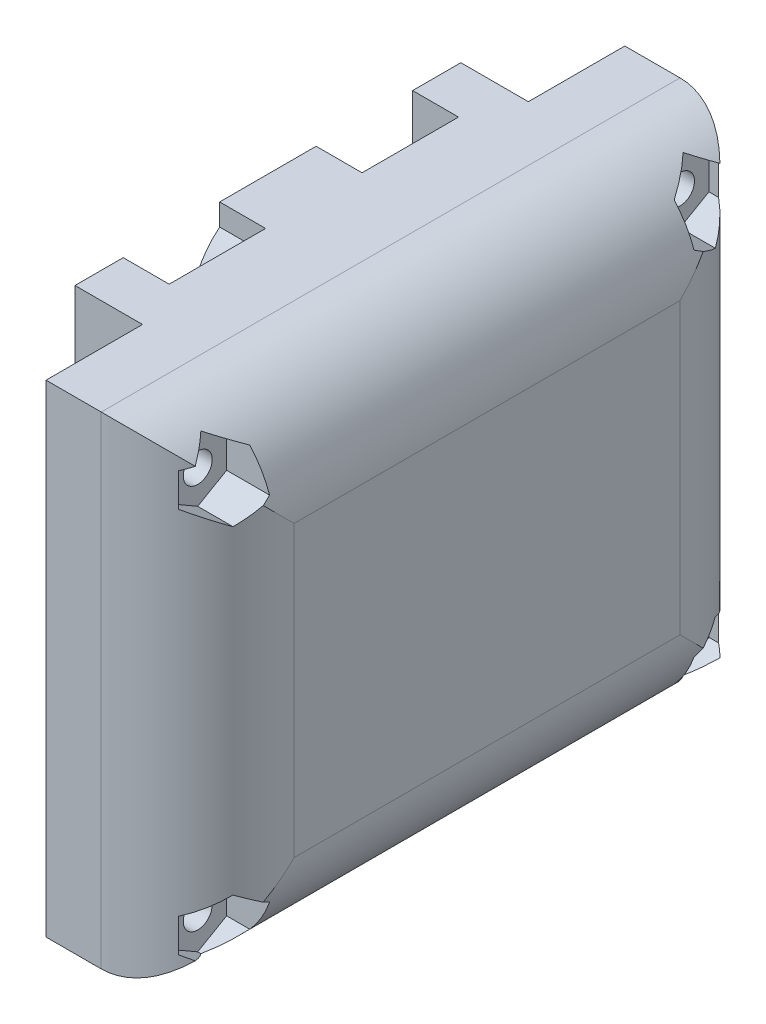
SolidWorks part; units mm, degrees
ref_plane "Alzado" through (0, 0, 0) normal (0, 0, 1) x (1, 0, 0)
ref_plane "Planta" through (0, 0, 0) normal (0, 1, 0) x (1, 0, 0)
ref_plane "Vista lateral" through (0, 0, 0) normal (1, 0, 0) x (0, 0, -1)
sketch "Croquis1" plane through (0, 0, 0) normal (1, 0, 0) x (0, 0, -1)
  line L0 (0, 0) -> (0, 16.1453) construction
  line L1 (-30, -25) -> (30, -25)
  line L2 (-30, -25) -> (-30, 25)
  line L3 (-30, 25) -> (30, 25)
  line L4 (30, -25) -> (30, 25)
  line L5 (-30, -25) -> (30, 25) construction
  line L6 (-30, 25) -> (30, -25) construction
  line L7 (0, 0) -> (-19.1227, 0) construction
  circle A0 centre (-25, 20) radius 1.5
  circle A1 centre (25, 20) radius 1.5
  circle A2 centre (25, -20) radius 1.5
  circle A3 centre (-25, -20) radius 1.5
  point P0 (0, 0)
  dimension "D3" = 3
  dimension "D1" = 60
  dimension "D2" = 50
  dimension "D4" = 5
  dimension "D5" = 5
extrude "Saliente-Extruir1" add sketch "Croquis1" along normal blind 17.96
sketch "Croquis3" plane through (0, 0, 0) normal (-1, 0, 0) x (0, 0, 1)
  line L0 (30, -25) -> (-30, -25) construction
  line L1 (-30, 25) -> (-15, 25)
  line L2 (-30, 25) -> (-30, -25)
  line L3 (-30, -25) -> (-15, -25)
  line L4 (-15, 25) -> (-15, -25)
  line L5 (0, 0) -> (0, -25) construction
  line L6 (30, -25) -> (15, -25)
  line L7 (15, 25) -> (15, -25)
  line L8 (30, 25) -> (15, 25)
  line L9 (30, 25) -> (30, -25)
  circle A0 centre (25, -20) radius 1.5 construction
  circle A1 centre (25, 20) radius 1.5 construction
  circle A2 centre (-25, -20) radius 1.5 construction
  circle A3 centre (-25, 20) radius 1.5 construction
  circle A4 centre (25, -20) radius 1.5
  circle A5 centre (25, 20) radius 1.5
  circle A6 centre (-25, -20) radius 1.5
  circle A7 centre (-25, 20) radius 1.5
  dimension "D1" = 30
extrude "Saliente-Extruir2" add sketch "Croquis3" along normal blind 4.7625
sketch "Croquis4" plane through (0, 0, 0) normal (-1, 0, 0) x (0, 0, 1)
  line L0 (0, 16.5) -> (0, -16.5) construction
  line L1 (-15, 25) -> (15, 25) construction
  line L3 (-5, 22.745) -> (-5, 25)
  line L4 (-5, 25) -> (5, 25)
  line L5 (5, 22.745) -> (5, 25)
  line L6 (-4.0562, 9.6045) -> (4.0562, 23.3955) construction
  line L7 (-4.0562, 23.3955) -> (4.0562, 9.6045) construction
  line L9 (-5, -22.745) -> (-5, -25)
  line L10 (-5, -25) -> (5, -25)
  line L11 (5, -22.745) -> (5, -25)
  line L12 (-4.0562, -9.6045) -> (5, -25) construction
  line L13 (-5, -25) -> (4.0562, -9.6045) construction
  line L14 (15, -25) -> (-15, -25) construction
  arc A0 (-5, 22.745) -> (5, 22.745) centre (0, 16.5) ccw
  arc A1 (5, -22.745) -> (-5, -22.745) centre (0, -16.5) ccw
  point P6 (0, 0)
  dimension "D1" = 16
  dimension "D2" = 16
  dimension "D3" = 33
  dimension "D4" = 10
  dimension "D5" = 10
extrude "Saliente-Extruir3" add sketch "Croquis4" along normal blind 4.7625
fillet "Redondeo2" radius 10 4 edges at (17.96, 0, -30) (17.96, 25, 0) (17.96, -25, 0) (17.96, 0, 30)
sketch "Croquis5" plane through (17.96, 0, 0) normal (1, 0, 0) x (0, 0, -1)
  line L1 (-25, 23.4641) -> (-28, 21.7321)
  line L2 (-28, 21.7321) -> (-28, 18.2679)
  line L3 (-28, 18.2679) -> (-25, 16.5359)
  line L4 (-25, 16.5359) -> (-22, 18.2679)
  line L5 (-22, 18.2679) -> (-22, 21.7321)
  line L6 (-22, 21.7321) -> (-25, 23.4641)
  line L7 (25, 23.4641) -> (22, 21.7321)
  line L8 (22, 21.7321) -> (22, 18.2679)
  line L9 (22, 18.2679) -> (25, 16.5359)
  line L10 (25, 16.5359) -> (28, 18.2679)
  line L11 (28, 18.2679) -> (28, 21.7321)
  line L12 (28, 21.7321) -> (25, 23.4641)
  line L13 (25, -16.5359) -> (22, -18.2679)
  line L14 (22, -18.2679) -> (22, -21.7321)
  line L15 (22, -21.7321) -> (25, -23.4641)
  line L16 (25, -23.4641) -> (28, -21.7321)
  line L17 (28, -21.7321) -> (28, -18.2679)
  line L18 (28, -18.2679) -> (25, -16.5359)
  line L19 (-25, -16.5359) -> (-28, -18.2679)
  line L20 (-28, -18.2679) -> (-28, -21.7321)
  line L21 (-28, -21.7321) -> (-25, -23.4641)
  line L22 (-25, -23.4641) -> (-22, -21.7321)
  line L23 (-22, -21.7321) -> (-22, -18.2679)
  line L24 (-22, -18.2679) -> (-25, -16.5359)
  circle A0 centre (-25, 20) radius 3 construction
  circle A1 centre (25, 20) radius 3 construction
  circle A2 centre (25, -20) radius 3 construction
  circle A3 centre (-25, -20) radius 3 construction
  dimension "D1" = 6
  dimension "D2" = 6
  dimension "D3" = 6
  dimension "D4" = 6
extrude "Cortar-Extruir1" cut sketch "Croquis5" against normal blind 5
sketch "Croquis6" plane through (-4.7625, 0, 0) normal (-1, 0, 0) x (0, 0, 1)
  line L0 (15, -25) -> (30, -25) construction
  line L1 (30, 25) -> (20, 25)
  line L2 (30, 25) -> (30, -25)
  line L3 (30, -25) -> (20, -25)
  line L4 (20, 25) -> (20, -25)
  line L5 (-30, -25) -> (-15, -25) construction
  line L6 (-30, 25) -> (-20, 25)
  line L7 (-30, 25) -> (-30, -25)
  line L8 (-30, -25) -> (-20, -25)
  line L9 (-20, 25) -> (-20, -25)
  line L10 (-25, 20) -> (-30, 20) construction
  dimension "D1" = 10
  dimension "D2" = 10
extrude "Cortar-Extruir2" cut sketch "Croquis6" against normal blind 7
